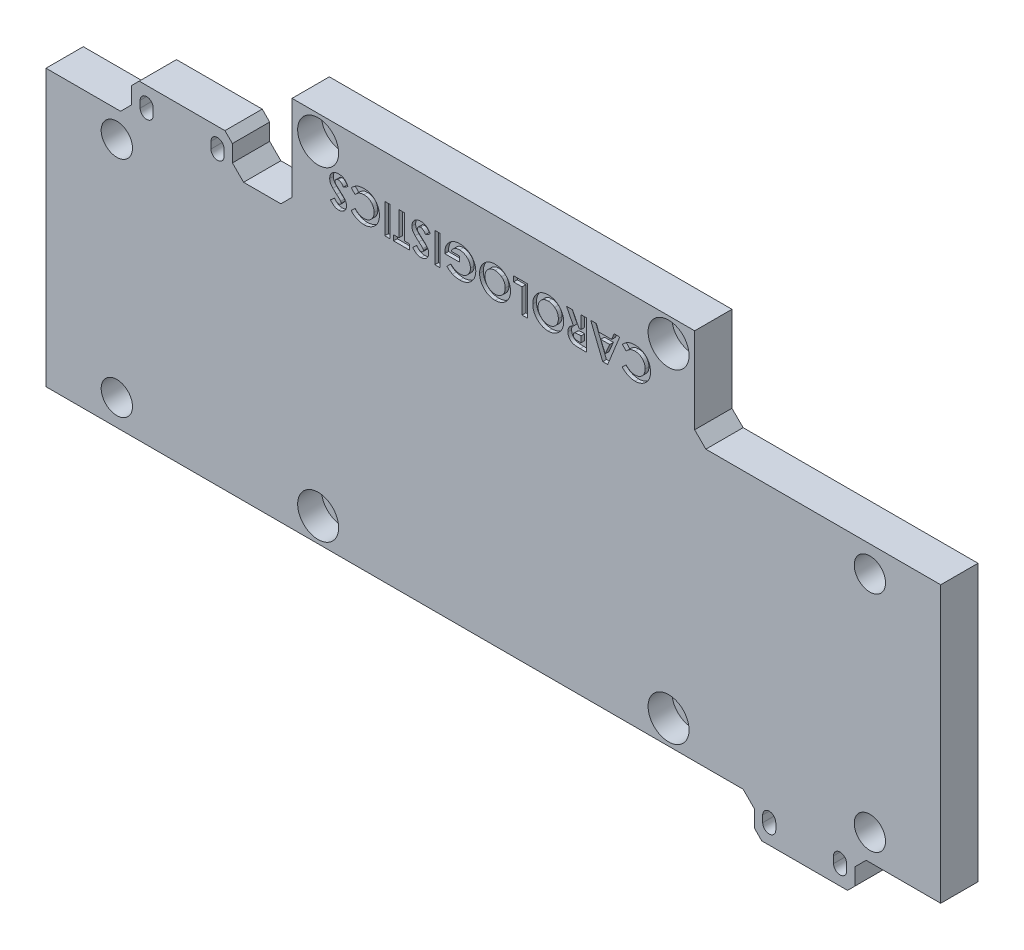
SolidWorks part; units mm, degrees
material "ABS"
ref_plane "Ebene vorne" through (0, 0, 0) normal (0, 0, 1) x (1, 0, 0)
ref_plane "Ebene oben" through (0, 0, 0) normal (0, 1, 0) x (1, 0, 0)
ref_plane "Ebene rechts" through (0, 0, 0) normal (1, 0, 0) x (0, 0, -1)
sketch "Skizze1" plane through (0, 0, 0) normal (0, 0, 1) x (1, 0, 0)
  line L1 (120, -50) -> (-120, -50)
  line L2 (120, -50) -> (120, 50)
  line L3 (120, 50) -> (-120, 50)
  line L4 (-120, -50) -> (-120, 50)
  line L5 (120, -50) -> (-120, 50) construction
  line L6 (120, 50) -> (-120, -50) construction
  point P0 (0, 0)
  dimension "D1" = 100
  dimension "D2" = 240
extrude "Aufsatz-Linear austragen1" add sketch "Skizze1" along normal blind 10
sketch "Skizze2" plane through (0, 0, 10) normal (0, 0, 1) x (1, 0, 0)
  line L1 (47, -43.5) -> (-47, -43.5)
  line L2 (47, -43.5) -> (47, 43.5)
  line L3 (47, 43.5) -> (-47, 43.5)
  line L4 (-47, -43.5) -> (-47, 43.5)
  line L5 (47, -43.5) -> (-47, 43.5) construction
  line L6 (47, 43.5) -> (-47, -43.5) construction
  point P0 (0, 0)
  dimension "D1" = 94
  dimension "D2" = 87
hole_wizard "Stirnsenkung für M6 Zylinderschraube mit Innensechskant1" positions "Skizze3" profile "Skizze4" counterbore size "M6" standard "DIN"
sketch "Skizze3" plane through (0, 0, 10) normal (0, 0, 1) x (1, 0, 0)
  point P0 (-47, -43.5)
  point P3 (47, -43.5)
sketch "Skizze4" plane through (-47, -43.5, 10) normal (1, 0, 0) x (0, -1, 0)
  line L0 (0, 0) -> (0, 16.9828)
  line L1 (0, 16.9828) -> (3.3, 15)
  line L2 (3.3, 15) -> (3.3, 6.4)
  line L3 (3.3, 6.4) -> (5.5, 6.4)
  line L4 (5.5, 6.4) -> (5.5, 0)
  line L5 (5.5, 0) -> (0, 0)
  line L10 (0, 16.9828) -> (-3.3, 15) construction
  line L11 (0, -6.35) -> (0, 107.95) construction
  dimension "Bohrerdurchmesser" = 6.6
  dimension "Bohrungstiefe" = 15
  dimension "Senkdurchmesser2" = 11
  dimension "Senktiefe2" = 6.4
  dimension "Spitzenwinkel" = 118
hole_wizard "CBORE for M6 Hex Socket Head Cap Screw1" positions "Skizze5" profile "Skizze6" counterbore size "M6" standard "DIN"
sketch "Skizze5" plane through (0, 0, 10) normal (0, 0, 1) x (1, 0, 0)
  point P0 (-47, 43.5)
  point P3 (47, 43.5)
sketch "Skizze6" plane through (-47, 43.5, 10) normal (1, 0, 0) x (0, -1, 0)
  line L0 (0, 0) -> (0, 16.9828)
  line L1 (0, 16.9828) -> (3.3, 15)
  line L2 (3.3, 15) -> (3.3, 6.4)
  line L3 (3.3, 6.4) -> (5.5, 6.4)
  line L4 (5.5, 6.4) -> (5.5, 0)
  line L5 (5.5, 0) -> (0, 0)
  line L10 (0, 16.9828) -> (-3.3, 15) construction
  line L11 (0, -6.35) -> (0, 107.95) construction
  dimension "Hole Dia." = 6.6
  dimension "Hole Depth" = 15
  dimension "C'Bore Dia." = 11
  dimension "C'Bore Depth" = 6.4
  dimension "Drill Angle" = 118
sketch "Skizze15" plane through (0, 0, 10) normal (0, 0, 1) x (1, 0, 0)
  line L0 (-120, -50) -> (120, -50) construction
  line L1 (101, -43) -> (-101, -43)
  line L2 (101, -43) -> (101, 17)
  line L3 (101, 17) -> (-101, 17)
  line L4 (-101, -43) -> (-101, 17)
  line L5 (-120, 50) -> (-120, -50) construction
  line L6 (120, -50) -> (120, 50) construction
  dimension "D1" = 60
  dimension "D2" = 19
  dimension "D3" = 7
  dimension "D4" = 19
hole_wizard "M8 Clearance Hole1" positions "Skizze16" profile "Skizze17" hole size "M8" standard "ISO"
sketch "Skizze16" plane through (0, 0, 10) normal (0, 0, 1) x (1, 0, 0)
  point P0 (-101, 17)
  point P3 (-101, -43)
  point P6 (101, 17)
  point P9 (101, -43)
sketch "Skizze17" plane through (-101, 17, 10) normal (1, 0, 0) x (0, -1, 0)
  line L0 (0, 0) -> (0, 19.5236)
  line L1 (0, 19.5236) -> (4.2, 17)
  line L2 (4.2, 17) -> (4.2, 0)
  line L5 (4.2, 0) -> (0, 0)
  line L10 (0, 19.5236) -> (-4.2, 17) construction
  line L11 (0, -6.35) -> (0, 107.95) construction
  dimension "Bohrerdurchmesser" = 8.4
  dimension "Bohrungstiefe" = 17
  dimension "Spitzenwinkel" = 118
sketch "Skizze18" plane through (0, 0, 10) normal (0, 0, 1) x (1, 0, 0)
  line L0 (-120, -50) -> (120, -50) construction
  line L1 (-120, 50) -> (-54, 50)
  line L2 (-120, 50) -> (-120, 24)
  line L3 (-120, 24) -> (-54, 24)
  line L4 (-54, 50) -> (-54, 24)
  dimension "D1" = 74
  dimension "D2" = 54
extrude "Schnitt-Linear austragen1" cut sketch "Skizze18" against normal blind 15
mirror "Spiegeln1" about plane through (0, 0, 0) normal (1, 0, 0) of "Schnitt-Linear austragen1"
sketch "Sketch1" plane through (0, 24, 0) normal (0, 1, 0) x (1, 0, 0)
  line L0 (120, 0) -> (54, 0) construction
  line L1 (97, 0) -> (70, 0)
  line L2 (97, 0) -> (97, -10)
  line L3 (97, -10) -> (70, -10)
  line L4 (70, 0) -> (70, -10)
  line L5 (120, -10) -> (54, -10) construction
  line L6 (120, 0) -> (120, -10) construction
  dimension "D1" = 23
  dimension "D2" = 27
extrude "Boss-Extrude1" add sketch "Sketch1" along normal blind 9.5
sketch "Sketch3" plane through (0, 0, 0) normal (0, 0, -1) x (-1, 0, 0)
  line L0 (-93, 29.15) -> (-93, 27.35) construction
  line L1 (-91.25, 29.15) -> (-91.25, 27.35)
  line L2 (-94.75, 29.15) -> (-94.75, 27.35)
  line L4 (-97, 33.5) -> (-70, 33.5) construction
  line L5 (-97, 33.5) -> (-97, 24) construction
  arc A0 (-91.25, 29.15) -> (-94.75, 29.15) centre (-93, 29.15) ccw
  arc A1 (-94.75, 27.35) -> (-91.25, 27.35) centre (-93, 27.35) ccw
  point P2 (-93, 28.25)
  dimension "D1" = 3.5
  dimension "D2" = 1.8
  dimension "D3" = 5.25
  dimension "D4" = 4
extrude "Cut-Extrude1" cut sketch "Sketch3" against normal blind 10
pattern_linear "LPattern1" count 2 spacing 19 along (-1, 0, 0) of "Cut-Extrude1"
sketch "Sketch4" plane through (0, 0, 10) normal (0, 0, 1) x (1, 0, 0)
  line L1 (74, 32.3832) -> (71.2, 30.7666)
  line L2 (71.2, 30.7666) -> (71.2, 28.3753)
  line L5 (76.8, 28.3728) -> (76.8, 30.7666)
  line L6 (76.8, 30.7666) -> (74, 32.3832)
  line L7 (71.2, 27.5334) -> (74, 25.9168) [skipped]
  line L8 (74, 25.9168) -> (76.8, 27.5334) [skipped]
  line L16 (74, 24.1168) -> (76.8, 25.7334)
  line L18 (76.8, 25.7334) -> (76.8, 28.3728)
  line L21 (71.2, 28.3753) -> (71.2, 25.7334)
  line L22 (71.2, 25.7334) -> (74, 24.1168)
  line L23 (74, 30.5832) -> (71.2, 28.9666) [skipped]
  line L24 (76.8, 28.9666) -> (74, 30.5832) [skipped]
  circle A0 centre (74, 29.15) radius 2.8 construction
  circle A1 centre (74, 27.35) radius 2.8 construction
  dimension "D2" = 5.6
  dimension "D1" = 5.6
extrude "Cut-Extrude2" cut sketch "Sketch4" along normal blind 3 from offset 10 offset against normal yes
pattern_linear "LPattern2" count 2 spacing 19 along (1, 0, 0) of "Cut-Extrude2"
ref_plane "Plane1" through (0, -13, 0) normal (0, 1, 0) x (1, 0, 0)
mirror "Mirror1" about plane through (0, -13, 0) normal (0, 1, 0) of "LPattern2", "Cut-Extrude2", "LPattern1", "Cut-Extrude1", "Boss-Extrude1"
sketch "Sketch5" plane through (0, 0, 10) normal (0, 0, 1) x (1, 0, 0)
  line L1 (70, 33.5) -> (97, 33.5)
  line L2 (70, 33.5) -> (70, 24)
  line L3 (70, 24) -> (97, 24)
  line L4 (97, 33.5) -> (97, 24)
extrude "Cut-Extrude3" cut sketch "Sketch5" against normal blind 10
sketch "Sketch6" plane through (0, 0, 10) normal (0, 0, 1) x (1, 0, 0)
  line L1 (54, 24) -> (84, 24)
  line L2 (54, 24) -> (54, 59)
  line L3 (54, 59) -> (84, 59)
  line L4 (84, 24) -> (84, 59)
  circle A0 centre (69, 55) radius 1.75
  circle A1 centre (69, 47) radius 1.75
  dimension "D3" = 3.5
  dimension "D4" = 3.5
  dimension "D7" = 4
  dimension "D8" = 8
  dimension "D1" = 30
  dimension "D2" = 35
  dimension "D5" = 15
  dimension "D6" = 15
mirror "Mirror2" about plane through (0, 0, 0) normal (1, 0, 0) of "LPattern2", "LPattern1", "Cut-Extrude1", "Boss-Extrude1", "Cut-Extrude2"
ref_plane "Plane2" through (0, 0, 20) normal (0, 0, 1) x (1, 0, 0)
chamfer "Chamfer1" distance 3 angle 45 4 edges at (-70, 24, 5) (-97, 24, 5) (97, -50, 5) (70, -50, 5)
chamfer "Chamfer3" distance 2 angle 45 4 edges at (-97, 33.5, 5) (-70, 33.5, 5) (70, -59.5, 5) (97, -59.5, 5)
chamfer "Chamfer4" distance 3 angle 45 2 edges at (-54, 24, 5) (54, 24, 5)
sketch "Sketch8" plane through (0, 0, 10) normal (0, 0, 1) x (1, 0, 0)
  line L0 (-54, 38.5) -> (54, 38.5) construction
  line L1 (-54, 27) -> (-54, 50) construction
  line L2 (54, 27) -> (54, 50) construction
  text T0 "<b>CAROLOGISTICS</b>" font "Century Gothic" height 8
extrude "Cut-Extrude4" cut sketch "Sketch8" against normal blind 1
